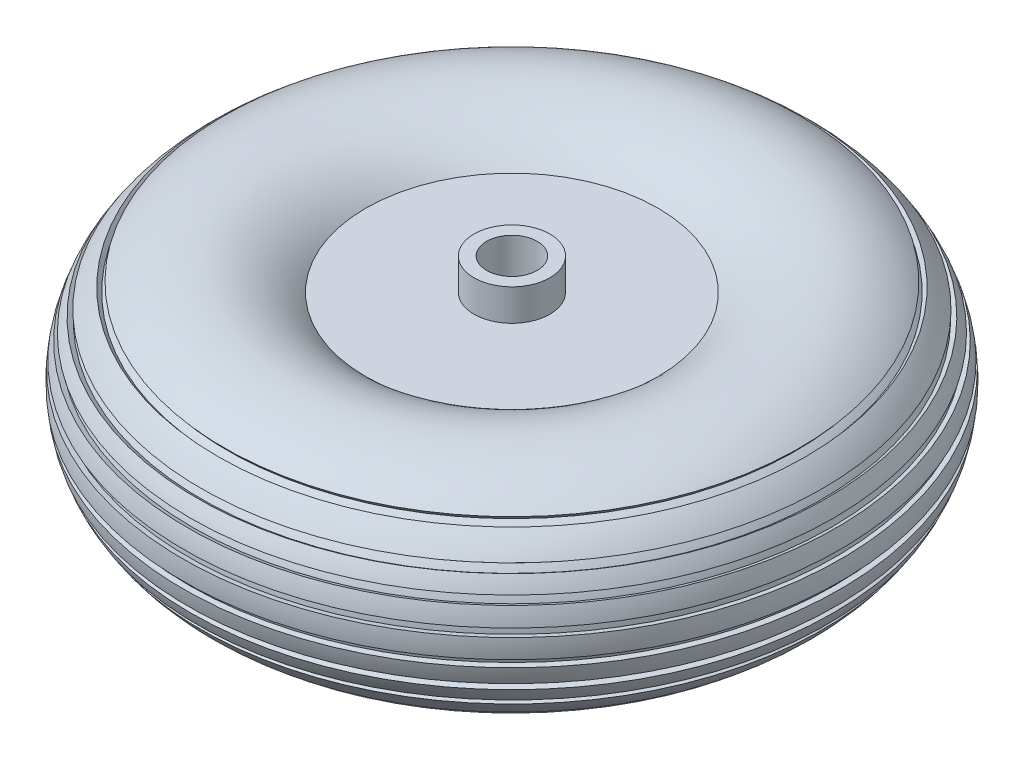
SolidWorks part; units mm, degrees
ref_plane "Front Plane" through (0, 0, 0) normal (1, 0, 0) x (0, 1, 0)
ref_plane "Top Plane" through (0, 0, 0) normal (0, 0, 1) x (0, 1, 0)
ref_plane "Right Plane" through (0, 0, 0) normal (0, 1, 0) x (-1, 0, 0)
sketch "Sketch2" plane through (0, 0, 0) normal (1, 0, 0) x (0, 1, 0)
  line L0 (0, 22.676) -> (0, 65.0707)
  line L1 (-6.4642, 62.5628) -> (-6.799, 64.6287)
  line L2 (-30, -7.428) -> (-30, -51.7948)
  line L3 (30, -51.7948) -> (30, -7.428)
  line L4 (-21.6439, 59.2519) -> (-20.4806, 57.5083)
  line L5 (-13.3922, 63.0108) -> (-12.5922, 61.0711)
  line L6 (-30.1684, 49.5574) -> (-31.7309, 50.9497)
  line L7 (-33.6464, 48.6408) -> (-32.0347, 47.3037)
  line L8 (-22.98, 55.9125) -> (-24.1702, 57.6339)
  line L9 (-15.4063, 60.0309) -> (-16.2043, 61.9656)
  line L10 (-3.799, 65.0059) -> (-3.468, 62.9341)
  line L11 (3.799, 65.0059) -> (3.468, 62.9341)
  line L12 (6.4642, 62.5628) -> (6.799, 64.6287)
  line L13 (15.4063, 60.0309) -> (16.2043, 61.9656)
  line L14 (13.3922, 63.0108) -> (12.5922, 61.0711)
  line L15 (22.98, 55.9125) -> (24.1702, 57.6339)
  line L16 (21.6439, 59.2519) -> (20.4806, 57.5083)
  line L17 (30.1684, 49.5574) -> (31.7309, 50.9497)
  line L18 (33.6464, 48.6408) -> (32.0347, 47.3037)
  line L19 (30, -20.176) -> (30, -65.176)
  line L20 (-30, -55.176) -> (-30, -65.176)
  line L21 (-30, -65.176) -> (30, -65.176)
  line L22 (30, -65.176) -> (-30, -65.176)
  line L23 (-30, -65.176) -> (-30, -55.176)
  line L24 (-30, -51.7948) -> (-30, -55.176) construction
  line L25 (-30, -51.7948) -> (-30, -65.176)
  line L26 (30, -65.176) -> (30, -51.7948)
  line L27 (-30, -51.7948) -> (-30, -65.176)
  line L28 (-30, -65.176) -> (30, -65.176)
  line L29 (30, -51.7948) -> (30, -65.176)
  line L30 (-30, -55.176) -> (30, -55.176)
  arc A0 (30, -7.428) -> (33.6464, 48.6408) centre (0, 22.676) ccw
  arc A1 (-32.0347, 47.3037) -> (-30.1684, 49.5574) centre (0, 22.676) cw
  arc A2 (-22.98, 55.9125) -> (-20.4806, 57.5083) centre (0, 22.676) cw
  arc A3 (-15.4063, 60.0309) -> (-12.5922, 61.0711) centre (0, 22.676) cw
  arc A4 (-6.4642, 62.5628) -> (-3.468, 62.9341) centre (0, 22.676) cw
  arc A5 (6.4642, 62.5628) -> (3.468, 62.9341) centre (0, 22.676) ccw
  arc A6 (15.4063, 60.0309) -> (12.5922, 61.0711) centre (0, 22.676) ccw
  arc A7 (22.98, 55.9125) -> (20.4806, 57.5083) centre (0, 22.676) ccw
  arc A8 (32.0347, 47.3037) -> (30.1684, 49.5574) centre (0, 22.676) ccw
  arc A9 (-33.6464, 48.6408) -> (-30, -7.428) centre (0, 22.676) ccw
  arc A10 (-24.1702, 57.6339) -> (-31.7309, 50.9497) centre (0, 22.676) ccw
  arc A11 (-16.2043, 61.9656) -> (-21.6439, 59.2519) centre (0, 22.676) ccw
  arc A12 (-6.799, 64.6287) -> (-13.3922, 63.0108) centre (0, 22.676) ccw
  arc A13 (3.799, 65.0059) -> (-3.799, 65.0059) centre (0, 22.676) ccw
  arc A14 (13.3922, 63.0108) -> (6.799, 64.6287) centre (0, 22.676) ccw
  arc A15 (21.6439, 59.2519) -> (16.2043, 61.9656) centre (0, 22.676) ccw
  arc A16 (31.7309, 50.9497) -> (24.1702, 57.6339) centre (0, 22.676) ccw
  point P6 (0, 22.676)
  point P8 (-7.8266, 48.5355)
  dimension "D1" = 85
  dimension "D2" = 3
  dimension "D3" = 3
  dimension "D4" = 44.3669
  dimension "D5" = 45
  dimension "D6" = 10
revolve "Revolve1" add sketch "Sketch2" angle 360 about L21 region at (0, 0, 5.3243)
sketch "Sketch3" plane through (0, -30, 0) normal (0, -1, 0) x (1, 0, 0)
  circle A0 centre (0, -65.176) radius 10
  circle A1 centre (0, -65.176) radius 15
  dimension "D1" = 30
extrude "Boss-Extrude1" add sketch "Sketch3" along normal blind 12.5
sketch "Sketch4" plane through (0, 30, 0) normal (0, 1, 0) x (-1, 0, 0)
  circle A0 centre (0, -65.176) radius 15
  circle A1 centre (0, -65.176) radius 10
  dimension "D1" = 30
extrude "Boss-Extrude2" add sketch "Sketch4" along normal blind 12.5
